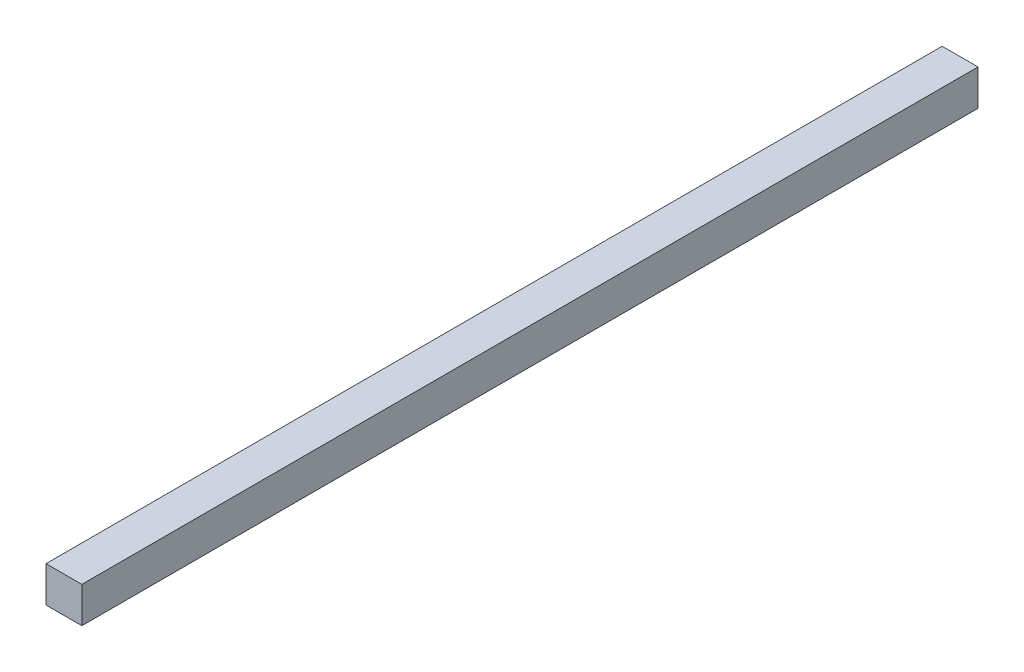
SolidWorks part; units mm, degrees
ref_plane "Front Plane" through (0, 0, 0) normal (0, 0, 1) x (1, 0, 0)
ref_plane "Top Plane" through (0, 0, 0) normal (0, 1, 0) x (1, 0, 0)
ref_plane "Right Plane" through (0, 0, 0) normal (1, 0, 0) x (0, 0, -1)
sketch "Sketch1" plane through (0, 0, 0) normal (0, 0, 1) x (1, 0, 0)
  line L1 (-66.4482, 13.9811) -> (-26.4482, 13.9811)
  line L2 (-66.4482, 13.9811) -> (-66.4482, -26.0189)
  line L3 (-66.4482, -26.0189) -> (-26.4482, -26.0189)
  line L4 (-26.4482, 13.9811) -> (-26.4482, -26.0189)
  dimension "D1" = 40
  dimension "D2" = 40
extrude "Boss-Extrude1" add sketch "Sketch1" along normal blind 1000
